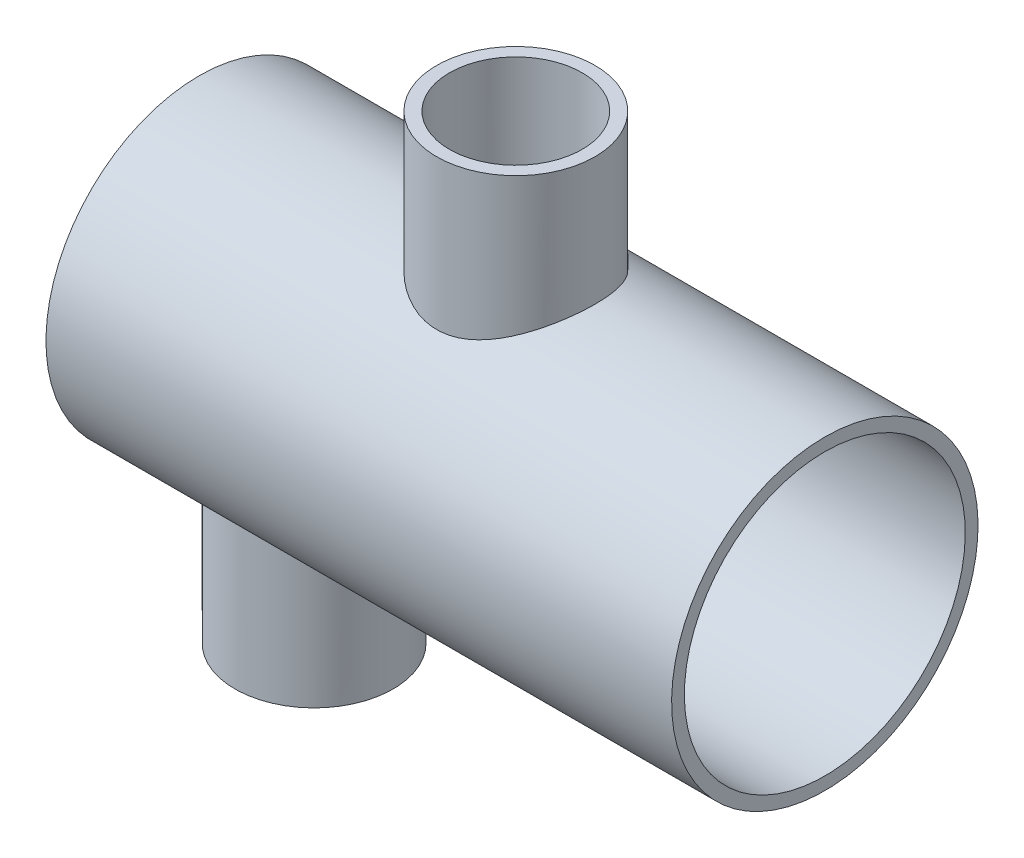
SolidWorks part; units mm, degrees
material "Acciaio al carbonio semplice"
ref_plane "Piano frontale" through (0, 0, 0) normal (0, 0, 1) x (1, 0, 0)
ref_plane "Piano superiore" through (0, 0, 0) normal (0, 1, 0) x (1, 0, 0)
ref_plane "Piano destro" through (0, 0, 0) normal (1, 0, 0) x (0, 0, -1)
sketch "Schizzo1" plane through (0, 0, 0) normal (0, 0, 1) x (1, 0, 0)
  line L0 (0, 0) -> (0, 12) construction
  line L1 (0, 12) -> (49, 12)
  line L2 (49, 12) -> (49, 0) construction
  line L3 (49, 0) -> (0, 0) construction
  line L4 (0, 0) -> (49, 0) construction
  dimension "D1" = 49
  dimension "D2" = 24
revolve "Rivoluzione-Sottile2" add sketch "Schizzo1" angle 360 about L3
ref_plane "Piano1" through (0, -12, 0) normal (0, -1, 0) x (-1, 0, 0)
sketch "Schizzo2" plane through (0, -12, 0) normal (0, -1, 0) x (-1, 0, 0)
  circle A0 centre (-9, 0) radius 5.2
  dimension "D2" = 10.4
  dimension "D1" = 9
ref_plane "Piano2" through (0, 12, 0) normal (0, 1, 0) x (1, 0, 0)
sketch "Schizzo3" plane through (0, 12, 0) normal (0, 1, 0) x (1, 0, 0)
  circle A0 centre (24.8, 0) radius 5.2
  dimension "D1" = 10.4
  dimension "D2" = 24.8
extrude "Estrusione-Sottile1" add sketch "Schizzo2" against normal up to surface and the other way blind 10 thin contours A0
extrude "Estrusione-Sottile2" add sketch "Schizzo3" against normal up to surface and the other way blind 10 thin contours A0
sketch "Schizzo4" plane through (0, -22, 0) normal (0, -1, 0) x (1, 0, 0)
  circle A0 centre (9, 0) radius 5.2
  circle A1 centre (9, 0) radius 5.2 construction
extrude "Taglio-Estrusione2" cut sketch "Schizzo4" against normal blind 15
sketch "Schizzo5" plane through (0, 22, 0) normal (0, 1, 0) x (1, 0, 0)
  circle A0 centre (24.8, 0) radius 5.2
  circle A1 centre (24.8, 0) radius 5.2 construction
extrude "Taglio-Estrusione3" cut sketch "Schizzo5" against normal blind 15
sketch "Schizzo6" plane through (0, 0, 0) normal (0, 0, 1) x (1, 0, 0)
  line L0 (15.2, 11) -> (15.2, 10)
  line L1 (15.2, 10) -> (14.2, 10)
  line L2 (14.2, 10) -> (14.2, 11)
  line L3 (15.2, 11) -> (14.2, 11)
  line L4 (13.2, 12) -> (-13.2, 12) construction
  line L5 (0, 0) -> (22.4251, 0) construction
  line L6 (0, 11) -> (0, -11) construction
  dimension "D1" = 1
  dimension "D2" = 1
  dimension "D3" = 15.2
  dimension "D4" = 1
revolve "Rivoluzione1" add sketch "Schizzo6" angle 360 about L5
fillet "Raccordo1" radius 1 1 edges at (15.2, 0, 11)
